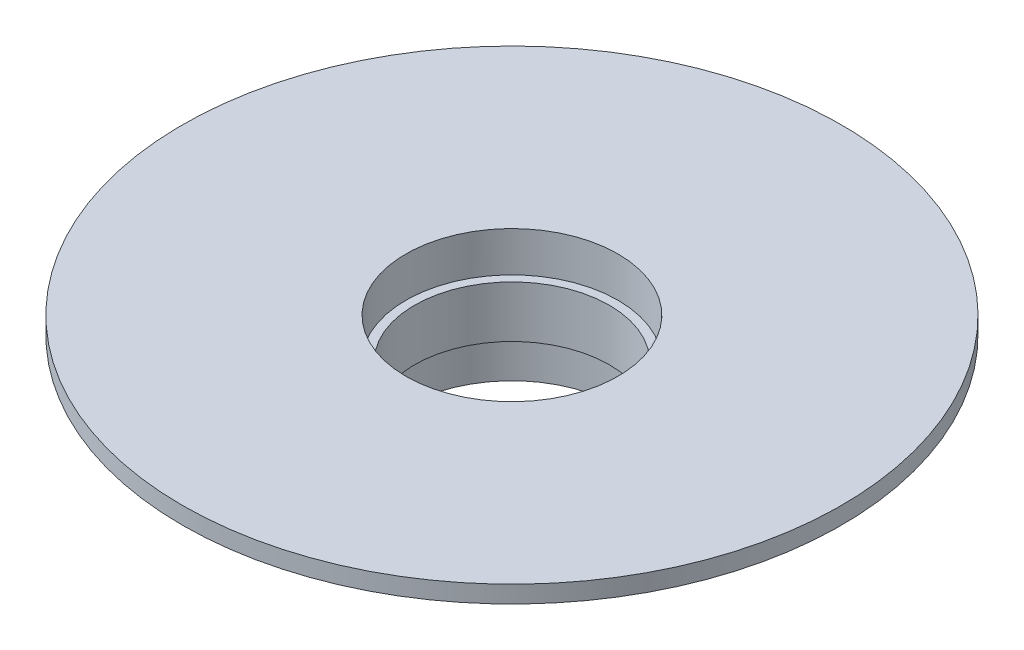
SolidWorks part; units mm, degrees
ref_plane "Front Plane" through (0, 0, 0) normal (0, 0, 1) x (1, 0, 0)
ref_plane "Top Plane" through (0, 0, 0) normal (0, 1, 0) x (1, 0, 0)
ref_plane "Right Plane" through (0, 0, 0) normal (1, 0, 0) x (0, 0, -1)
sketch "Sketch1" plane through (0, 0, 0) normal (0, 1, 0) x (1, 0, 0)
  circle A0 centre (0, 0) radius 57.5
  circle A1 centre (0, 0) radius 18.5
  dimension "D1" = 115
  dimension "D2" = 37
extrude "Boss-Extrude1" add sketch "Sketch1" along normal blind 3 contours A1 | A0 region at (0, 0, 0)
sketch "Sketch2" plane through (0, 0, 0) normal (0, -1, 0) x (1, 0, 0)
  circle A0 centre (0, 0) radius 45
  circle A1 centre (0, 0) radius 18.5 construction
  circle A2 centre (0, 0) radius 18.5
  circle M3 centre (0, 0) radius 18.5
  dimension "D1" = 90
extrude "Boss-Extrude2" add sketch "Sketch2" along normal blind 2 contours M3 | A0 region at (0, 0, 0)
sketch "Sketch3" plane through (0, -2, 0) normal (0, -1, 0) x (1, 0, 0)
  circle A0 centre (0, 0) radius 21
  circle A1 centre (0, 0) radius 18.5
  dimension "D1" = 42
  dimension "D2" = 37
extrude "Boss-Extrude3" add sketch "Sketch3" along normal blind 18
sketch "Sketch4" plane through (0, -20, 0) normal (0, -1, 0) x (1, 0, 0)
  circle A0 centre (0, 0) radius 17
  circle A1 centre (0, 0) radius 18.5 construction
  circle A2 centre (0, 0) radius 18.5
  dimension "D1" = 34
extrude "Boss-Extrude4" add sketch "Sketch4" against normal blind 9 from offset 7 contours A0 | A2 offset against normal yes
